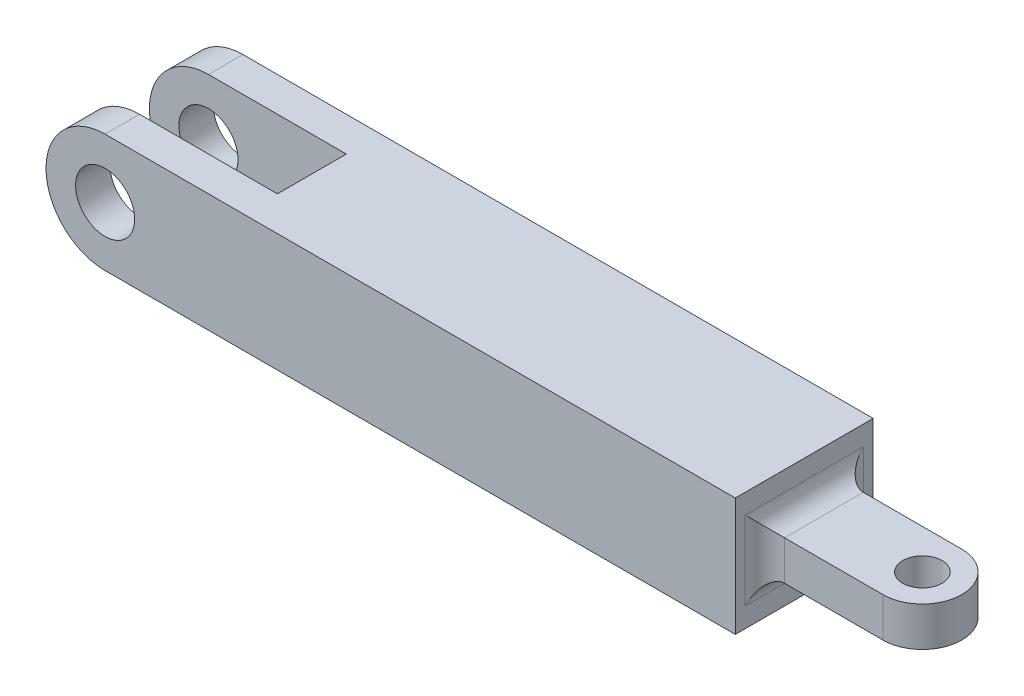
SolidWorks part; units mm, degrees
ref_plane "Front Plane" through (0, 0, 0) normal (0, 0, 1) x (1, 0, 0)
ref_plane "Top Plane" through (0, 0, 0) normal (0, 1, 0) x (1, 0, 0)
ref_plane "Right Plane" through (0, 0, 0) normal (1, 0, 0) x (0, 0, -1)
sketch "Sketch1" plane through (0, 0, 0) normal (0, 0, 1) x (1, 0, 0)
  line L0 (0, 0) -> (0, 12)
  line L1 (0, 12) -> (-64, 12)
  line L2 (-64, 0) -> (0, 0)
  arc A0 (-64, 12) -> (-64, 0) centre (-64, 6) ccw
  point P6 (0, 0)
  point P8 (-64, -3.8161)
  point P9 (0, 0)
  dimension "D1" = 6
  dimension "D2" = 64
extrude "Boss-Extrude1" add sketch "Sketch1" along normal mid plane 14
sketch "Sketch2" plane through (0, 0, 0) normal (1, 0, 0) x (0, 0, -1)
  line L0 (0, 12) -> (0, 0) construction
  line L4 (7, 0) -> (7, 12)
  line L5 (7, 12) -> (-7, 12)
  line L6 (-7, 12) -> (-7, 0)
  line L7 (-7, 0) -> (7, 0)
  line L8 (7, 0) -> (7, 12)
  line L9 (7, 12) -> (-7, 12)
  line L10 (-7, 12) -> (-7, 0)
  line L11 (-7, 0) -> (7, 0)
  line L13 (-4, 4) -> (4, 4)
  line L14 (-4, 4) -> (-4, 8)
  line L15 (-4, 8) -> (4, 8)
  line L16 (4, 4) -> (4, 8)
  line L17 (-4, 4) -> (4, 8) construction
  line L18 (-4, 8) -> (4, 4) construction
  line L20 (-7, 6) -> (7, 6) construction
  point P2 (0, 6)
  point P12 (0, 6)
  dimension "D2" = 4
  dimension "D3" = 3
  dimension "D1" = 0
extrude "Boss-Extrude2" add sketch "Sketch2" along normal blind 16 contours L14 L13 L16 L15
fillet "Fillet1" 2 edges at (16, 6, 4) (16, 6, -4) type full round first side face at (8, 6, 4) second side face at (8, 6, -4) middle face at (16, 6, 0)
sketch "Sketch3" plane through (0, 8, 0) normal (0, 1, 0) x (1, 0, 0)
  line L3 (0, -4) -> (12, -4)
  line L4 (12, 4) -> (0, 4)
  line L5 (0, 4) -> (0, -4)
  line L6 (0, -4) -> (12, -4)
  line L7 (12, 4) -> (0, 4)
  line L8 (0, 4) -> (0, -4)
  circle A0 centre (12, 0) radius 2
  arc A1 (12, -4) -> (12, 4) centre (12, 0) ccw
  arc A2 (12, -4) -> (12, 4) centre (12, 0) ccw
  dimension "D2" = 4
  dimension "D1" = 0
extrude "Cut-Extrude1" cut sketch "Sketch3" against normal blind 16 contours A0 region at (12, 8, 0)
sketch "Sketch5" plane through (0, 12, 0) normal (0, 1, 0) x (1, 0, 0)
  line L0 (-70, 7) -> (-70, -7) construction
  line L1 (-70, -7) -> (-64, -7) construction
  line L2 (-70, 7) -> (-70, -7)
  line L3 (-70, -7) -> (-64, -7)
  line L4 (0, 7) -> (-64, 7)
  line L5 (-64, 7) -> (-64, -7)
  line L6 (-64, -7) -> (0, -7)
  line L7 (0, -7) -> (0, 7)
  line L8 (0, 7) -> (-64, 7)
  line L9 (-64, 7) -> (-64, -7)
  line L10 (-64, -7) -> (0, -7)
  line L11 (0, -7) -> (0, 7)
  line L12 (-70, 0) -> (16, 0) construction
  line L14 (-50, -3.5) -> (-90, -3.5)
  line L15 (-50, -3.5) -> (-50, 3.5)
  line L16 (-50, 3.5) -> (-90, 3.5)
  line L17 (-90, -3.5) -> (-90, 3.5)
  line L18 (-50, -3.5) -> (-90, 3.5) construction
  line L19 (-50, 3.5) -> (-90, -3.5) construction
  arc A0 (12, -4) -> (12, 4) centre (12, 0) ccw construction
  dimension "D2" = 40
  dimension "D3" = 3.5
  dimension "D1" = 0
extrude "Cut-Extrude2" cut sketch "Sketch5" against normal blind 33 contours L17 L14 L2 L16 | L15 L16 L9 L14 | L9 L16 L2 L14 region at (-67, 12, 0) region at (-80, 12, 0) region at (-57, 12, 0)
sketch "Sketch6" plane through (0, 0, 7) normal (0, 0, 1) x (1, 0, 0)
  line L3 (-64, 0) -> (0, 0)
  line L4 (0, 0) -> (0, 12)
  line L5 (0, 12) -> (-64, 12)
  line L6 (-64, 0) -> (0, 0)
  line L7 (0, 0) -> (0, 12)
  line L8 (0, 12) -> (-64, 12)
  circle A0 centre (-64, 6) radius 3
  arc A1 (-64, 12) -> (-64, 0) centre (-64, 6) ccw
  arc A2 (-64, 12) -> (-64, 0) centre (-64, 6) ccw
  dimension "D2" = 6
  dimension "D1" = 0
extrude "Cut-Extrude3" cut sketch "Sketch6" against normal through all both and the other way through all contours A0
fillet "Fillet2" radius 2 4 edges at (0, 6, 4) (0, 8, 0) (0, 6, -4) (0, 4, 0)
